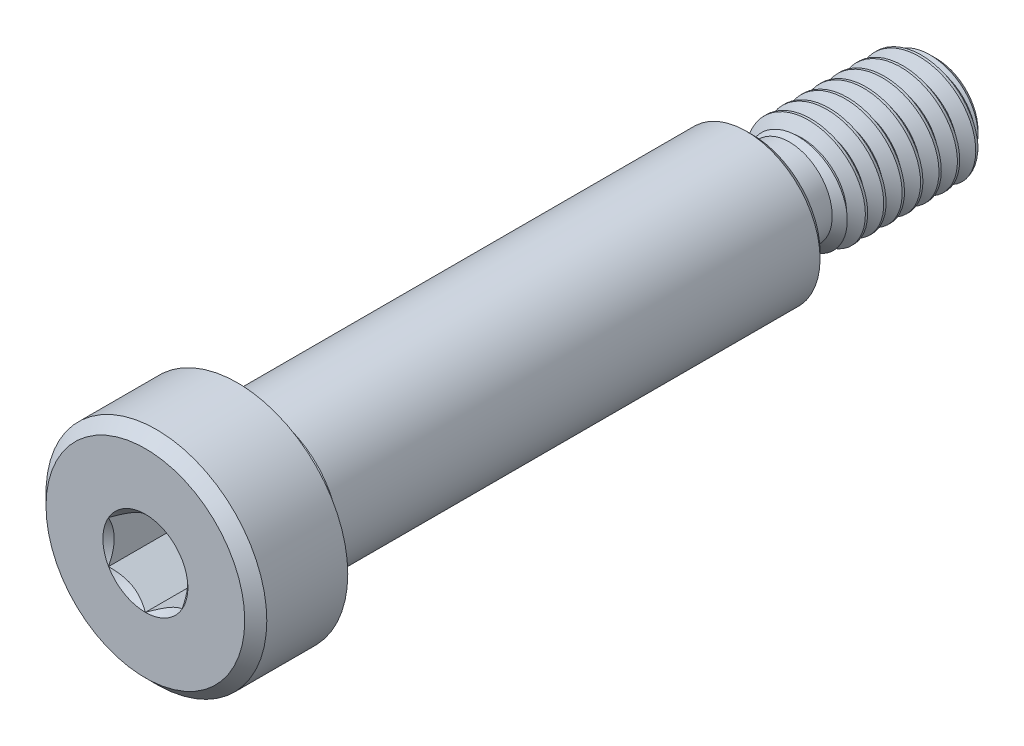
SolidWorks part; units mm, degrees
material "Plain Carbon Steel"
ref_plane "Front Plane" through (0, 0, 0) normal (0, 0, 1) x (1, 0, 0)
ref_plane "Top Plane" through (0, 0, 0) normal (0, 1, 0) x (1, 0, 0)
ref_plane "Right Plane" through (0, 0, 0) normal (1, 0, 0) x (0, 0, -1)
sketch "Sketch2" plane through (0, 0, 0) normal (1, 0, 0) x (0, 0, -1)
  line L0 (-34.1313, 0) -> (34.1313, 0) construction
  line L1 (-34.1313, 0) -> (-34.1313, 9.525)
  line L2 (-34.1313, 9.525) -> (-26.1938, 9.525)
  line L3 (-26.1938, 9.525) -> (-26.1938, 6.35)
  line L4 (-26.1938, 6.35) -> (18.2562, 6.35)
  line L5 (18.2562, 4.7625) -> (34.1312, 4.7625)
  line L6 (34.1312, 4.7625) -> (34.1313, 0)
  line L7 (34.032, 4.9344) -> (34.8258, 3.5595) construction
  line L8 (34.8258, 3.5595) -> (35.6195, 4.9344) construction
  line L9 (35.6195, 4.9344) -> (34.032, 4.9344) construction
  line L10 (34.1312, 4.7625) -> (35.5203, 4.7625) construction
  line L11 (34.8258, 4.9344) -> (34.8258, 4.7625) construction
  line L12 (34.8258, 4.7625) -> (34.8258, 3.7314) construction
  line L13 (34.8258, 3.7314) -> (34.8258, 3.5595) construction
  line L14 (34.7266, 3.7314) -> (34.925, 3.7314)
  line L15 (34.0816, 4.8484) -> (35.5699, 4.8484)
  line L16 (34.925, 3.7314) -> (35.5699, 4.8484)
  line L17 (34.7266, 3.7314) -> (34.0816, 4.8484)
  line L18 (34.1313, 0) -> (34.1312, -4.7625) construction
  line L19 (18.2562, -6.35) -> (18.2562, 0) construction
  line L20 (18.2562, 0) -> (18.2562, 6.35) construction
  line L21 (-34.1313, 0) -> (-34.1313, -9.525) construction
  point P11 (-23.8316, 6.35)
  point P12 (30.1625, -4.7625)
  point P22 (34.8258, 4.8484)
  point P23 (13.8112, 0)
  point P25 (-19.3866, 0)
  point P26 (-26.1938, -9.525)
  point P29 (18.2562, -6.35)
  dimension "Head Height" = 7.9375
  dimension "Shoulder Diameter" = 12.7
  dimension "Screw Size Decimal Equivalent" = 9.525
  dimension "Thread Length" = 15.875
  dimension "Head Diameter" = 19.05
  dimension "Undercut Length" = 2.3622
  dimension "Pitch" = 1.5875
  dimension "D2" = 0.1984
  dimension "D1" = 3.9688
  dimension "Shoulder Length" = 44.45
  dimension "D3" = 4.445
  dimension "D4" = 4.445
sketch "Sketch3" plane through (0, 0, 0) normal (0, 0, 1) x (1, 0, 0)
  line L1 (0, 3.6662) -> (-3.175, 1.8331)
  line L2 (-3.175, 1.8331) -> (-3.175, -1.8331)
  line L3 (-3.175, -1.8331) -> (0, -3.6662)
  line L4 (0, -3.6662) -> (3.175, -1.8331)
  line L5 (3.175, -1.8331) -> (3.175, 1.8331)
  line L6 (3.175, 1.8331) -> (0, 3.6662)
  circle A0 centre (0, 0) radius 3.175 construction
  dimension "Drive Size" = 6.35
sketch "Sketch4" plane through (0, 0, 0) normal (1, 0, 0) x (0, 0, -1)
  line L0 (-26.1938, 9.525) -> (-33.1788, 9.525)
  line L1 (-33.1788, 9.525) -> (-34.1313, 8.5725)
  line L2 (-26.1938, 9.525) -> (-26.1938, 6.35)
  line L3 (-26.1938, 6.35) -> (-25.8763, 6.0325)
  line L4 (-25.8763, 6.0325) -> (-24.1491, 6.0325)
  line L5 (-24.1491, 6.0325) -> (-23.8316, 6.35)
  line L6 (-26.1938, 6.35) -> (18.2562, 6.35) construction
  line L7 (-34.1313, 0) -> (34.1313, 0) construction
  line L8 (-23.8316, 6.35) -> (17.7271, 6.35)
  line L9 (17.7271, 6.35) -> (18.2562, 5.8208)
  line L10 (18.2562, 5.8208) -> (18.2562, 0)
  line L11 (18.2562, 6.35) -> (18.2562, 5.8208) construction
  line L12 (18.2562, 5.8208) -> (18.2562, 5.2917) construction
  line L13 (18.2562, 5.2917) -> (18.2562, 4.7625) construction
  line L14 (-34.1313, 8.5725) -> (-34.1313, 0)
  line L15 (-34.1313, 9.525) -> (-26.1938, 9.525) construction
  line L16 (-34.1313, 0) -> (18.2562, 0)
  dimension "D1" = 45
  dimension "D2" = 12.065
  dimension "D3" = 45
  dimension "D4" = 45
  dimension "D5" = 17.145
revolve "Revolve1" add sketch "Sketch4" angle 360 about L16
sketch "Sketch5" plane through (0, 0, 34.1313) normal (0, 0, 1) x (1, 0, 0)
  line L0 (3.175, 1.8331) -> (0, 3.6662) construction
  line L1 (3.175, -1.8331) -> (3.175, 1.8331) construction
  line L2 (0, -3.6662) -> (3.175, -1.8331) construction
  line L3 (-3.175, -1.8331) -> (0, -3.6662) construction
  line L4 (-3.175, 1.8331) -> (-3.175, -1.8331) construction
  line L5 (0, 3.6662) -> (-3.175, 1.8331) construction
  line L6 (3.175, 1.8331) -> (0, 3.6662)
  line L7 (3.175, -1.8331) -> (3.175, 1.8331)
  line L8 (0, -3.6662) -> (3.175, -1.8331)
  line L9 (-3.175, -1.8331) -> (0, -3.6662)
  line L10 (-3.175, 1.8331) -> (-3.175, -1.8331)
  line L11 (0, 3.6662) -> (-3.175, 1.8331)
extrude "Cut-Extrude1" cut sketch "Sketch5" against normal blind 5.9531
sketch "Sketch6" plane through (0, 0, 34.1313) normal (0, 0, 1) x (1, 0, 0)
  circle A0 centre (0, 0) radius 3.6662
extrude "Cut-Extrude4" cut sketch "Sketch6" against normal blind 5.9531 draft 45
sketch "Sketch7" plane through (0, 0, 0) normal (1, 0, 0) x (0, 0, -1)
  line L0 (18.2562, 4.7625) -> (32.9406, 4.7625)
  line L1 (18.2562, 4.7625) -> (34.1312, 4.7625) construction
  line L2 (32.9406, 4.7625) -> (34.1312, 3.5719)
  line L3 (34.1312, 4.7625) -> (34.1312, 0) construction
  line L4 (34.1312, 3.5719) -> (34.1313, 0)
  line L5 (34.1313, 0) -> (18.2562, 0)
  line L6 (18.2562, -5.8208) -> (18.2562, 5.8208) construction
  line L7 (18.2562, 0) -> (18.2562, 4.7625)
  dimension "D1" = 45
  dimension "D2" = 1.1906
revolve "Revolve2" add sketch "Sketch7" angle 360 about L5
sketch "Sketch10" plane through (0, 0, 0) normal (1, 0, 0) x (0, 0, -1)
  line L0 (19.323, 3.6957) -> (21.4312, 3.6957)
  line L1 (21.4312, 3.6957) -> (24.0856, 6.35)
  line L2 (24.0856, 6.35) -> (18.2562, 6.35)
  line L3 (18.2562, 6.35) -> (18.2562, 4.7625)
  line L4 (18.2562, -5.8208) -> (18.2562, 5.8208) construction
  line L5 (34.1313, 0) -> (18.2562, 0) construction
  line L6 (-34.1313, 0) -> (34.1313, 0) construction
  arc A0 (18.2562, 4.7625) -> (19.323, 3.6957) centre (19.323, 4.7625) ccw
  dimension "Flat OD" = 7.3914
  dimension "Flat" = 3.175
  dimension "D3" = 45
revolve "Cut-Revolve1" cut sketch "Sketch10" angle 360 about L5
sketch "Sketch8" plane through (0, 0, -34.1312) normal (0, 0, -1) x (-1, 0, 0)
  circle A0 centre (0, 0) radius 4.7625 construction
  circle A1 centre (0, 0) radius 4.7625
curve "Helix/Spiral1" pitch 1.5875 height 17.4625 radius 4.7625 centre (0, 0, -34.1312) axis (0, 0, 1) start towards (0, 1, 0)
sketch "Sketch9" plane through (0, 0, 0) normal (1, 0, 0) x (0, 0, -1)
  line L0 (34.7266, 3.7314) -> (34.925, 3.7314) construction
  line L1 (34.925, 3.7314) -> (35.5699, 4.8484) construction
  line L2 (34.0816, 4.8484) -> (35.5699, 4.8484) construction
  line L3 (34.7266, 3.7314) -> (34.0816, 4.8484) construction
  line L4 (34.7266, 3.7314) -> (34.925, 3.7314)
  line L5 (34.925, 3.7314) -> (35.5699, 4.8484)
  line L6 (34.0816, 4.8484) -> (35.5699, 4.8484)
  line L7 (34.7266, 3.7314) -> (34.0816, 4.8484)
ref_plane "Plane1" through (0, 0, -21.4312) normal (0, 0, 1) x (1, 0, 0)
split "Split1" trim tools "Plane1" bodies to split 138 resulting bodies 139 140
sweep "Cut-Sweep1" cut profiles "Sketch9" path "Helix/Spiral1" align with end faces yes
combine bodies "Combine1" operation type add bodies to combine 141 139
sketch "Sketch11" [suppressed] plane through (0, 0, 34.1313) normal (0, 0, 1) x (1, 0, 0)
  line L0 (-0.1375, 9.525) -> (0.1375, 9.525)
  line L1 (0.1375, 9.525) -> (0, 9.2869)
  line L2 (0, 0) -> (0, 9.525) construction
  line L3 (0, 9.2869) -> (-0.1375, 9.525)
  line L4 (0, 0) -> (9.525, 0) construction
  circle A0 centre (0, 0) radius 9.525 construction
  point P6 (0, 9.525)
  dimension "D1" = 18.5738
  dimension "D2" = 60
  dimension "D3" = 0.275
sketch "Sketch12" [suppressed] plane through (0, 0, 0) normal (1, 0, 0) x (0, 0, -1)
  line L0 (-34.1313, 9.2869) -> (-28.753, 9.2869)
  line L1 (-27.94, 10.0999) -> (-27.94, 9.525) construction
  line L2 (-34.1313, 9.525) -> (-26.1938, 9.525) construction
  arc A0 (-28.753, 9.2869) -> (-27.94, 10.0999) centre (-28.753, 10.0999) ccw
  point P11 (-28.1781, 9.525)
  dimension "D1" = 1.9844
sweep "Cut-Sweep2" [suppressed] cut profiles "Sketch11" path "Sketch12"
pattern_circular "CirPattern1" [suppressed] count 76 over 360 about axis through (0, 0, 34.1313) along (0, 0, -1) of bodies 143
equation "\"D2@Sketch2\" = \"Pitch@Sketch2\" / 8"
equation "\"D1@Sketch2\"=\"Pitch@Sketch2\"*2.5"
equation "\"D2@Sketch4\"=\"Shoulder Diameter@Sketch2\"*0.95"
equation "\"D5@Sketch4\"=\"Head Diameter@Sketch2\"*0.9"
equation "\"D1@Cut-Extrude1\"=\"Head Height@Sketch2\"*0.75"
equation "\"D1@Cut-Extrude4\"=\"D1@Cut-Extrude1\""
equation "\"D2@Sketch7\"=\"pitch@sketch2\"*0.75"
equation "\"D3@Helix/Spiral1\"=\"Thread Length@Sketch2\"+\"Pitch@Sketch2\""
equation "\"D4@Helix/Spiral1\"=\"Pitch@Sketch2\""
equation "\"D1@Sketch11\"=\"Head Diameter@Sketch2\"*0.975"
equation "\"D1@Sketch12\"=\"Head Height@Sketch2\"*0.25"
equation "\"D1@CirPattern1\"=\"Head Diameter@Sketch2\" * 3.14 / \"D3@Sketch11\" * 0.35"
equation "\"D3@Sketch2\"=\"D4@Sketch2\""
equation "\"D4@Sketch2\"=IF(\"Shoulder Length@Sketch2\"<.5,.05,(\"Shoulder Length@Sketch2\"*.1))"
